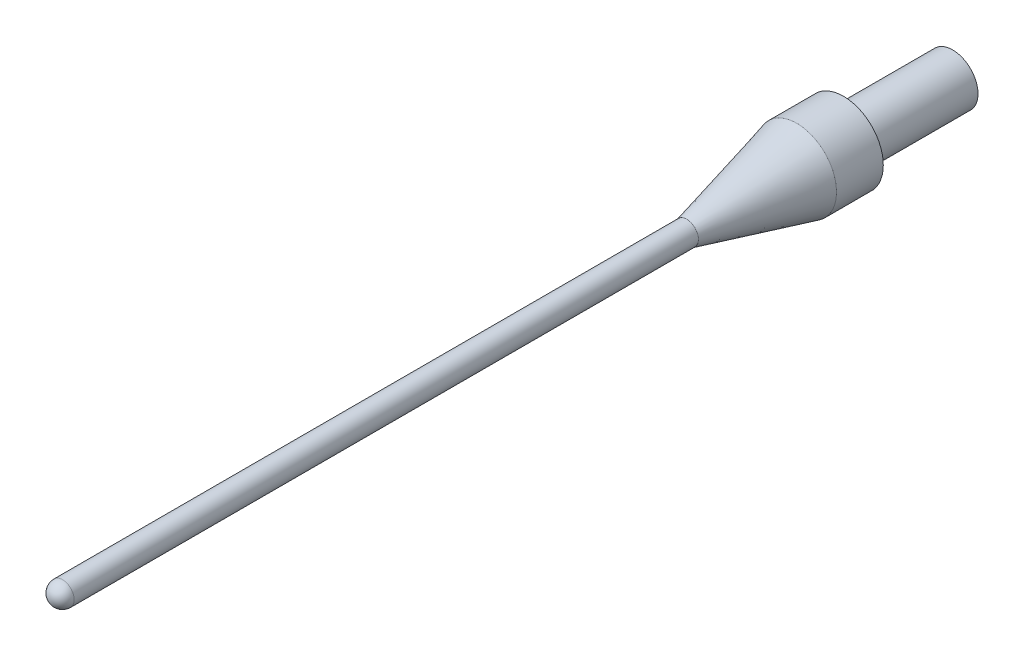
SolidWorks part; units mm, degrees
ref_plane "Plan de face" through (0, 0, 0) normal (0, 0, 1) x (1, 0, 0)
ref_plane "Plan de dessus" through (0, 0, 0) normal (0, 1, 0) x (1, 0, 0)
ref_plane "Plan de droite" through (0, 0, 0) normal (1, 0, 0) x (0, 0, -1)
sketch "Esquisse1" plane through (0, 0, 0) normal (0, 0, 1) x (1, 0, 0)
  circle A0 centre (0, 0) radius 8.5
  dimension "D1" = 17
extrude "Boss.-Extru.1" add sketch "Esquisse1" along normal blind 10 contours A0
sketch "Esquisse2" plane through (0, 0, 10) normal (0, 0, 1) x (1, 0, 0)
  circle A0 centre (0, 0) radius 2.5
  dimension "D1" = 5
extrude "Boss.-Extru.2" add sketch "Esquisse2" along normal blind 157
scale "Echelle2" scale about origin uniform scaling yes scale factor 0.6
sketch "Esquisse5" plane through (0, 0, 0) normal (0, 0, -1) x (-1, 0, 0)
  circle A0 centre (0, 0) radius 3.25
  dimension "D1" = 6.5
extrude "Boss.-Extru.4" add sketch "Esquisse5" along normal blind 14
sketch "Esquisse6" plane through (0, 0, -14) normal (0, 0, -1) x (-1, 0, 0)
  circle A0 centre (0, 0) radius 1
  dimension "D1" = 2
extrude "Enlèv. mat.-Extru.1" cut sketch "Esquisse6" against normal blind 17
sketch "Esquisse8" plane through (0, 0, 0) normal (0, 1, 0) x (1, 0, 0)
  line L0 (5.1, -6) -> (0, -6)
  line L1 (-5.1, -6) -> (5.1, -6) construction
  line L2 (0, -6) -> (0, -26)
  line L3 (0, -26) -> (5.1, -6)
  dimension "D1" = 20
revolve "Révolution1" add sketch "Esquisse8" angle 360 about L2
dome "Dôme1" faces to dome 1 distance 1.5 reverse direction no elliptical dome no face at (1.5, 0, 100.2) parameters "D1"=1.5
